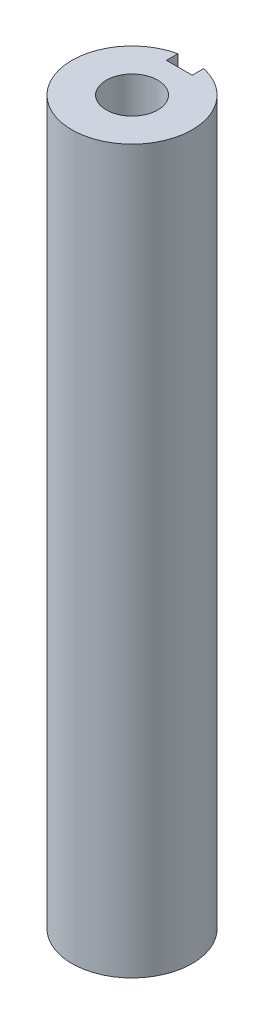
SolidWorks part; units mm, degrees
material "AISI 1045 Steel, cold drawn"
ref_plane "Front Plane" through (0, 0, 0) normal (0, 0, 1) x (1, 0, 0)
ref_plane "Top Plane" through (0, 0, 0) normal (0, 1, 0) x (1, 0, 0)
ref_plane "Right Plane" through (0, 0, 0) normal (1, 0, 0) x (0, 0, -1)
sketch "Sketch1" plane through (0, 0, 0) normal (0, 1, 0) x (1, 0, 0)
  line L0 (0, 0) -> (0, 74.8181) construction
  line L2 (-2.3813, 10.8544) -> (-2.3813, 8.7312)
  line L3 (-2.3813, 8.7312) -> (2.3813, 8.7312)
  line L4 (2.3813, 10.8544) -> (2.3813, 8.7312)
  line L5 (4.0598, 11.1125) -> (-6.0262, 11.1125) construction
  arc A1 (2.3813, 10.8544) -> (-2.3813, 10.8544) centre (0, 0) cw
  circle A2 centre (0, 0) radius 4.7625
  dimension "D1" = 6.35
  dimension "7/16" = 11.1125
  dimension "D2" = 4.7625
  dimension "D3" = 2.3813
extrude "Shaft" add sketch "Sketch1" along normal blind 133.35
sketch "Sketch3" plane through (0, 0, 0) normal (0, 0, 1) x (1, 0, 0)
  line L0 (0, 0) -> (0, 129.54)
  circle A0 centre (0, 129.54) radius 1.7859
  circle A1 centre (0, 129.54) radius 1.7859 construction
extrude "Cut-Extrude1" [suppressed] cut sketch "Sketch3" against normal through all both and the other way through all contours A0
chamfer "Chamfer1" [suppressed] distance 0.254 angle 45
